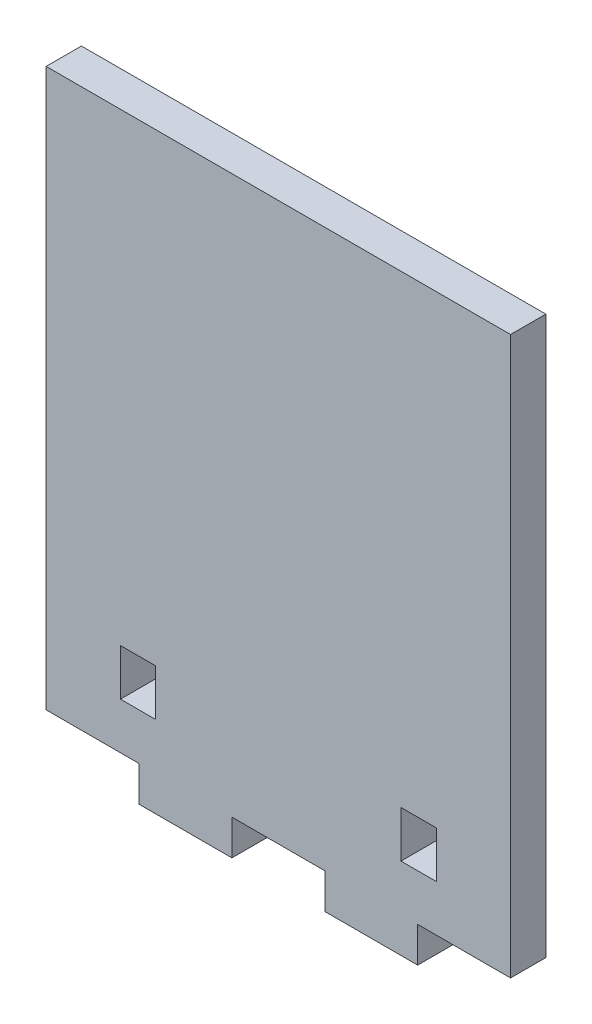
SolidWorks part; units mm, degrees
ref_plane "Front Plane" through (0, 0, 0) normal (0, 0, 1) x (1, 0, 0)
ref_plane "Top Plane" through (0, 0, 0) normal (0, 1, 0) x (1, 0, 0)
ref_plane "Right Plane" through (0, 0, 0) normal (1, 0, 0) x (0, 0, -1)
sketch "Sketch1" plane through (0, 0, 0) normal (0, 0, 1) x (1, 0, 0)
  line L1 (0, 0) -> (63.5, 0)
  line L2 (0, 0) -> (0, 81.026)
  line L3 (0, 81.026) -> (63.5, 81.026)
  line L4 (63.5, 0) -> (63.5, 81.026)
  dimension "D1" = 81.026
  dimension "D2" = 63.5
extrude "Boss-Extrude1" add sketch "Sketch1" along normal blind 4.826
sketch "Sketch2" plane through (0, 0, 4.826) normal (0, 0, 1) x (1, 0, 0)
  line L0 (0, 0) -> (63.5, 0) construction
  line L1 (0, 0) -> (12.7, 0)
  line L2 (0, 0) -> (0, 4.826)
  line L3 (0, 4.826) -> (12.7, 4.826)
  line L4 (12.7, 0) -> (12.7, 4.826)
  line L5 (25.4, 0) -> (38.1, 0)
  line L6 (25.4, 0) -> (25.4, 4.826)
  line L7 (25.4, 4.826) -> (38.1, 4.826)
  line L8 (38.1, 0) -> (38.1, 4.826)
  line L9 (12.7, 4.826) -> (25.4, 4.826) construction
  line L10 (63.5, 0) -> (50.8, 0)
  line L11 (63.5, 0) -> (63.5, 4.826)
  line L12 (63.5, 4.826) -> (50.8, 4.826)
  line L13 (50.8, 0) -> (50.8, 4.826)
  line L14 (38.1, 4.826) -> (50.8, 4.826) construction
  dimension "D1" = 4.826
extrude "Cut-Extrude1" cut sketch "Sketch2" against normal through all
sketch "Sketch3" plane through (0, 0, 0) normal (0, 0, -1) x (-1, 0, 0)
  line L0 (-53.34, 17.526) -> (-53.34, 11.176) construction
  line L1 (-53.34, 17.526) -> (-48.514, 17.526) construction
  line L2 (-48.514, 17.526) -> (-48.514, 11.176) construction
  line L3 (-53.34, 11.176) -> (-48.514, 11.176) construction
  line L4 (-14.986, 17.526) -> (-14.986, 11.176) construction
  line L5 (-14.986, 17.526) -> (-10.16, 17.526) construction
  line L6 (-10.16, 17.526) -> (-10.16, 11.176) construction
  line L7 (-14.986, 11.176) -> (-10.16, 11.176) construction
  line L8 (-53.34, 17.526) -> (-53.34, 11.176)
  line L9 (-53.34, 17.526) -> (-48.514, 17.526)
  line L10 (-48.514, 17.526) -> (-48.514, 11.176)
  line L11 (-53.34, 11.176) -> (-48.514, 11.176)
  line L12 (-50.8, 4.826) -> (-50.8, 0)
  line L13 (-50.8, 0) -> (-38.1, 0)
  line L14 (-38.1, 0) -> (-38.1, 4.826)
  line L15 (-38.1, 4.826) -> (-25.4, 4.826)
  line L16 (-25.4, 4.826) -> (-25.4, 0)
  line L17 (-25.4, 0) -> (-12.7, 0)
  line L18 (-12.7, 0) -> (-12.7, 4.826)
  line L19 (-12.7, 4.826) -> (0, 4.826)
  line L20 (0, 4.826) -> (0, 81.026)
  line L21 (0, 81.026) -> (-63.5, 81.026)
  line L22 (-63.5, 81.026) -> (-63.5, 4.826)
  line L23 (-63.5, 4.826) -> (-50.8, 4.826)
  line L24 (-50.8, 4.826) -> (-50.8, 0)
  line L25 (-50.8, 0) -> (-38.1, 0)
  line L26 (-38.1, 0) -> (-38.1, 4.826)
  line L27 (-38.1, 4.826) -> (-25.4, 4.826)
  line L28 (-25.4, 4.826) -> (-25.4, 0)
  line L29 (-25.4, 0) -> (-12.7, 0)
  line L30 (-12.7, 0) -> (-12.7, 4.826)
  line L31 (-12.7, 4.826) -> (0, 4.826)
  line L32 (0, 4.826) -> (0, 81.026)
  line L33 (0, 81.026) -> (-63.5, 81.026)
  line L34 (-63.5, 81.026) -> (-63.5, 4.826)
  line L35 (-63.5, 4.826) -> (-50.8, 4.826)
  line L36 (-14.986, 17.526) -> (-14.986, 11.176)
  line L37 (-14.986, 17.526) -> (-10.16, 17.526)
  line L38 (-10.16, 17.526) -> (-10.16, 11.176)
  line L39 (-14.986, 11.176) -> (-10.16, 11.176)
  dimension "D1" = 0
extrude "Cut-Extrude2" cut sketch "Sketch3" against normal blind 4.826 contours L8 L11 L10 L9 | L36 L39 L38 L37 region at (50.927, 14.351, 0) region at (12.573, 14.351, 0)
equation "\"MDF\"= 0.19in"
equation "\"PVCID\"= 2.067in"
equation "\"PVCOD\"= 2.375in"
equation "\"GenDiameter\"= 60mm"
equation "\"GenCutDiameter\"= 1.8in"
equation "\"GenCutDistance\"= 1"
equation "\"TowerHeight\"= 6in"
equation "\"TowerFrontBase\"= 3in"
equation "\"FunnelHeight\"= 1in"
equation "\"FunnelAngle\"= 20"
equation "\"TowerSideBase\"= 3in"
equation "\"TowerPanelLength\"= 2in"
equation "\"TowerPanelLeeway\"= 0.5in"
equation "\"BaseLength\"= 9in"
equation "\"BaseWidth\"= 10in"
equation "\"WheelHoleLength\"= 3.25in"
equation "\"WheelHoleWidth\"= 26mm"
equation "\"WheelHoleFromBack\"= 1.5in"
equation "\"DropLength\"= 1in"
equation "\"DropWidth\"= 8.5in"
equation "\"BumperWidth\"= 1in"
equation "\"SmallHexDiameter\"= 0.185in"
equation "\"SmallHexHeight\"= 0.701in"
equation "\"ScrewSize\"= 0.106in"
equation "\"BigHexDiameter\"= 0.251in"
equation "\"BigHexHeight\"= 0.374in"
equation "\"PCBThickness\"= 0.066in"
equation "\"ConnectorHeight\"= 0.517in"
equation "\"BoardHeight\"= 0.583in"
equation "\"UnoStackHeight\"= 1.351in"
equation "\"UnoStackWidth\"= 3.053in"
equation "\"UnoStackLength\"= 3.152in"
equation "\"HBridgeWidth\"= 1.797in"
equation "\"HBridgeLength\"= 2.236in"
equation "\"DSWidth\"= 1.820in"
equation "\"DSLength\"= 1.833in"
equation "\"StepperWidth\"= 1.799in"
equation "\"StepperLength\"= 2.248in"
equation "\"ULNWidth\"= 1.304in"
equation "\"ULNLength\"= 1.545in"
equation "\"VSwitchHeight\"= 0.392in"
equation "\"VSwitchWidth\"= 0.637in"
equation "\"VSwitchLength\"= 1.097in"
equation "\"SkateWheelDiameter\"= 80mm"
equation "\"SkateWheelThickness\"= 24mm"
equation "\"BaseDistance\"= 3in"
equation "\"DummyVar\"= 2in"
equation "\"D1@Sketch1\"=\"MDF\"+3in"
equation "\"D1@Boss-Extrude1\"=\"MDF\""
equation "\"D1@Sketch2\"=\"MDF\""
equation "\"D1@Cut-Extrude2\"=\"MDF\""
